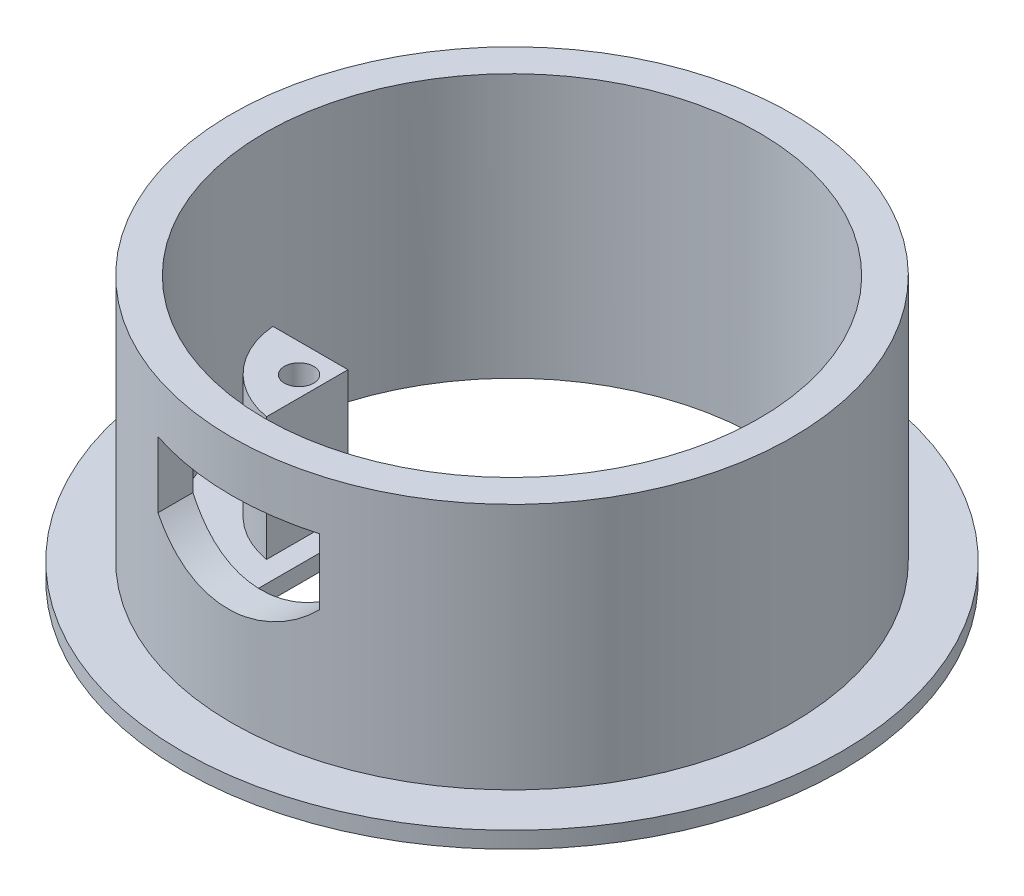
SolidWorks part; units mm, degrees
ref_plane "Front Plane" through (0, 0, 0) normal (0, 0, 1) x (1, 0, 0)
ref_plane "Top Plane" through (0, 0, 0) normal (0, 1, 0) x (1, 0, 0)
ref_plane "Right Plane" through (0, 0, 0) normal (1, 0, 0) x (0, 0, -1)
sketch "Sketch1" plane through (0, 0, 0) normal (0, 1, 0) x (1, 0, 0)
  circle A0 centre (0, 0) radius 40
  circle A1 centre (0, 0) radius 30
  dimension "D1" = 80
  dimension "D2" = 60
extrude "Boss-Extrude1" add sketch "Sketch1" along normal blind 2
sketch "Sketch2" plane through (0, 2, 0) normal (0, 1, 0) x (1, 0, 0)
  circle A0 centre (0, 0) radius 30 construction
  circle A1 centre (0, 0) radius 30
  circle A2 centre (0, 0) radius 34
  dimension "D1" = 4
extrude "Boss-Extrude2" add sketch "Sketch2" along normal blind 30
ref_plane "Plane1" through (0, 12, 0) normal (0, 1, 0) x (1, 0, 0)
sketch "Sketch9" plane through (0, 0, 0) normal (0, 1, 0) x (1, 0, 0)
  line L0 (-29.8657, -2.8351) -> (29.8657, -2.8351)
  line L1 (0, 30) -> (0, -48.3805) construction
  line L2 (-30, 0) -> (59.405, 0) construction
  circle A0 centre (0, 0) radius 30 construction
  arc A1 (29.8657, -2.8351) -> (0, -30) centre (0, 0) cw
  arc A2 (-29.8657, -2.8351) -> (0, -30) centre (0, 0) ccw
extrude "Boss-Extrude3" add sketch "Sketch9" along normal blind 2
sketch "Sketch11" plane through (0, 2, 0) normal (0, 1, 0) x (1, 0, 0)
  line L0 (-24.1735, -4.8351) -> (-15.0625, -4.8351)
  line L1 (-15.0625, -4.8351) -> (-15.0625, -14.7177)
  line L2 (0, 30) -> (0, 39.1404) construction
  line L3 (24.1735, -4.8351) -> (15.0625, -4.8351)
  line L4 (15.0625, -4.8351) -> (15.0625, -14.7177)
  line L5 (-29.8657, -2.8351) -> (29.8657, -2.8351) construction
  arc A0 (-24.1735, -4.8351) -> (-15.0625, -14.7177) centre (-13.1735, -3.8351) ccw
  arc A1 (24.1735, -4.8351) -> (15.0625, -14.7177) centre (13.1735, -3.8351) cw
  dimension "D1" = 2
ref_plane "Plane2" through (0, 0, 35) normal (0, 0, 1) x (1, 0, 0)
sketch "Sketch10" plane through (0, 0, 35) normal (0, 0, 1) x (1, 0, 0)
  line L0 (-10.6683, 25.8895) -> (9.3317, 25.8895)
  line L1 (9.3317, 25.8895) -> (9.3317, 17.8895)
  line L2 (-10.6683, 25.8895) -> (-10.6683, 17.8895)
  arc A0 (9.3317, 17.8895) -> (-10.6683, 17.8895) centre (-0.6683, 27.8895) cw
extrude "Cut-Extrude1" cut sketch "Sketch10" against normal blind 7
extrude "Boss-Extrude4" add sketch "Sketch11" along normal blind 15
sketch "Sketch12" plane through (0, 17, 0) normal (0, 1, 0) x (1, 0, 0)
  line L0 (0, 0) -> (0, 7.1822) construction
  line L1 (0, 30) -> (0, -48.3805) construction
  line L2 (-15.0625, -4.8351) -> (-24.1735, -4.8351) construction
  circle A0 centre (-17.5, -8.3351) radius 1.775
  circle A1 centre (17.5, -8.3351) radius 1.775
  dimension "D1" = 35
  dimension "D2" = 3.5
extrude "Cut-Extrude2" cut sketch "Sketch12" against normal blind 9
sketch "Sketch13" plane through (0, 2, 0) normal (0, 1, 0) x (1, 0, 0)
  line L0 (-12.5209, -20.7984) -> (-12.5209, 1.2016)
  line L1 (-12.5209, 1.2016) -> (13.4791, 1.2016)
  line L2 (13.4791, 1.2016) -> (13.4791, -20.7984)
  arc A0 (13.4791, -20.7984) -> (-12.5209, -20.7984) centre (0.4791, -7.7984) cw
extrude "Cut-Extrude3" cut sketch "Sketch13" against normal blind 10
